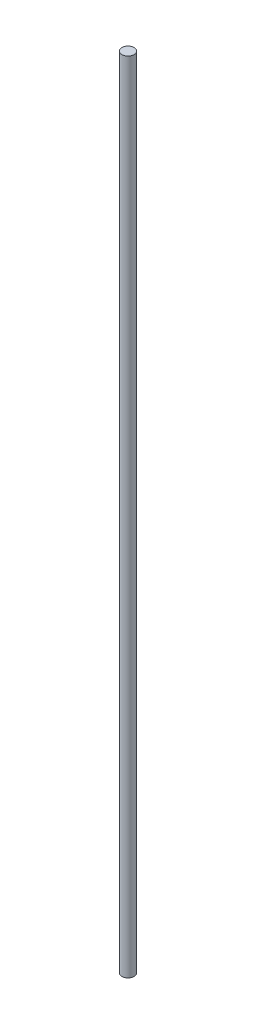
SolidWorks part; units mm, degrees
material "Hexcel AS4C (3000 Filaments)"
ref_plane "Front Plane" through (0, 0, 0) normal (0, 0, 1) x (1, 0, 0)
ref_plane "Top Plane" through (0, 0, 0) normal (0, 1, 0) x (1, 0, 0)
ref_plane "Right Plane" through (0, 0, 0) normal (1, 0, 0) x (0, 0, -1)
sketch "Sketch1" plane through (0, 0, 0) normal (0, 1, 0) x (1, 0, 0)
  circle A0 centre (0, 0) radius 1
  dimension "D1" = 2
extrude "Boss-Extrude1" add sketch "Sketch1" along normal mid plane 130
